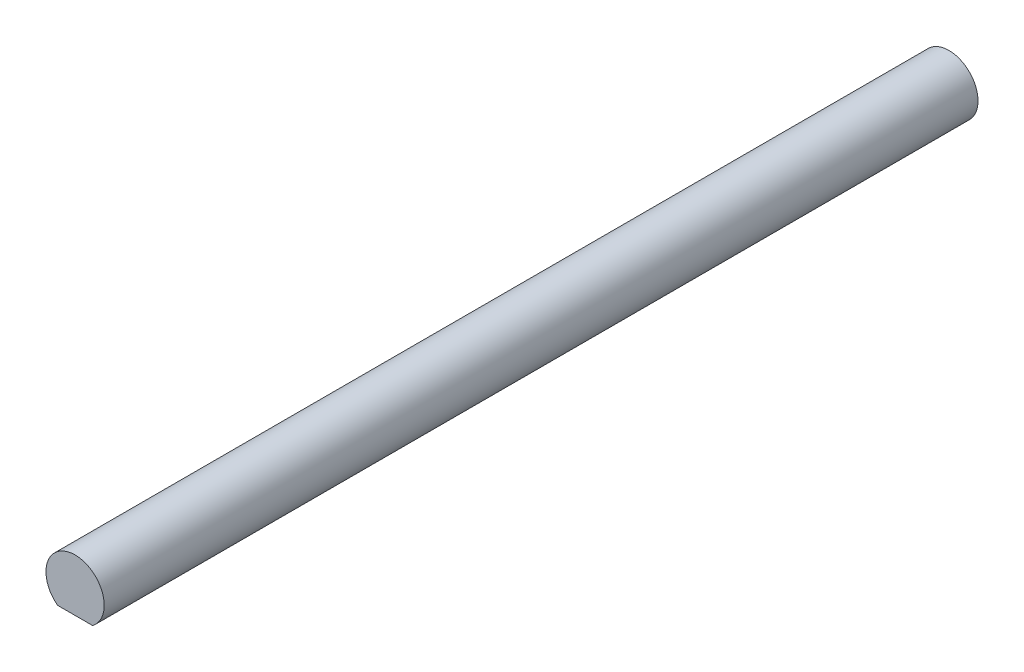
SolidWorks part; units mm, degrees
ref_plane "Front Plane" through (0, 0, 0) normal (0, 0, 1) x (1, 0, 0)
ref_plane "Top Plane" through (0, 0, 0) normal (0, 1, 0) x (1, 0, 0)
ref_plane "Right Plane" through (0, 0, 0) normal (1, 0, 0) x (0, 0, -1)
sketch "Sketch1" plane through (0, 0, 0) normal (0, 0, 1) x (1, 0, 0)
  line L0 (-1.905, -2.54) -> (1.905, -2.54)
  line L1 (0, 3.175) -> (0, -2.54) construction
  circle A0 centre (0, 0) radius 3.175
  dimension "D1" = 6.35
  dimension "D2" = 5.715
extrude "Boss-Extrude1" add sketch "Sketch1" along normal blind 47.625 and the other way blind 47.625 contours L1 A0 L0 | A0 L1 L0 region at (-1.3817, 0.1535, 0) region at (1.3817, 0.1535, 0)
ref_axis "Axis1" through (0, 0, -47.625) along (0, 0, 1)
